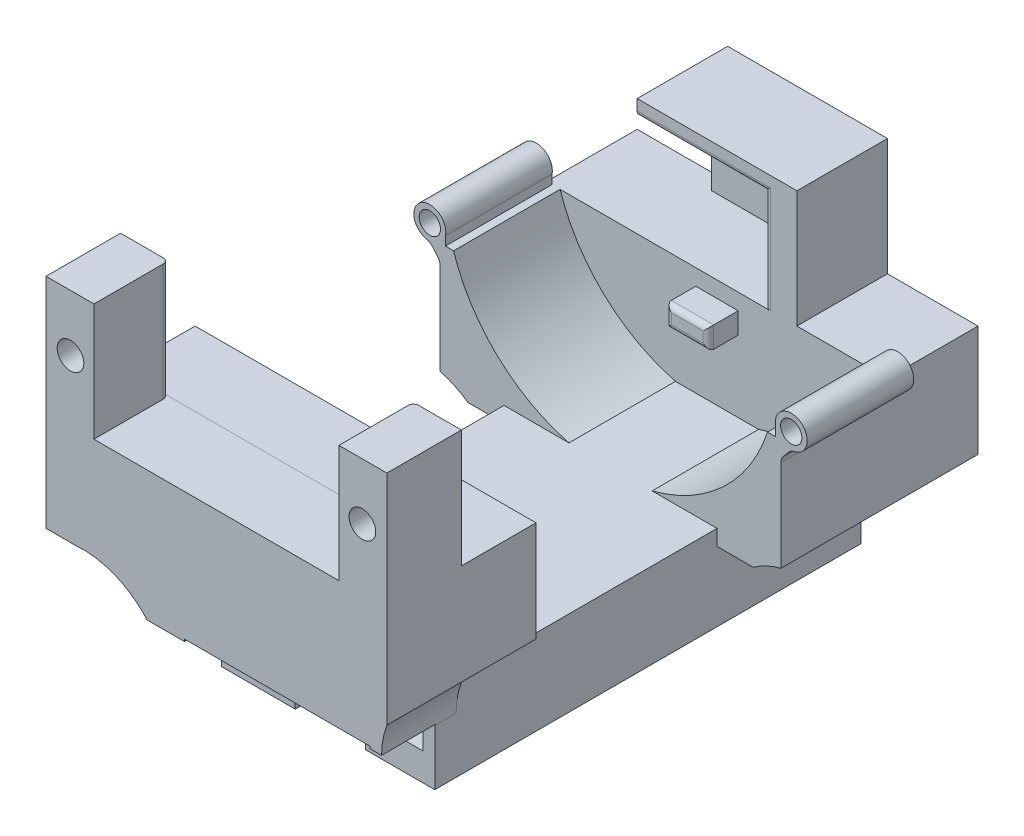
SolidWorks part; units mm, degrees
ref_plane "Front Plane" through (0, 0, 0) normal (0, 0, 1) x (1, 0, 0)
ref_plane "Top Plane" through (0, 0, 0) normal (0, 1, 0) x (1, 0, 0)
ref_plane "Right Plane" through (0, 0, 0) normal (1, 0, 0) x (0, 0, -1)
sketch "Sketch1" plane through (0, 0, 0) normal (0, 0, 1) x (1, 0, 0)
  line L0 (-6.3496, 0) -> (-0.9496, 0)
  line L1 (-0.9496, 0) -> (-0.9496, -2.6)
  line L2 (-0.9496, -2.6) -> (-7.8496, -2.6)
  line L3 (-7.8496, -2.6) -> (-7.8496, 5.4)
  line L4 (-7.8496, 5.4) -> (12.1504, 5.4)
  line L5 (12.1504, 5.4) -> (12.1504, -2.6)
  line L6 (12.1504, -2.6) -> (5.6504, -2.6)
  line L7 (5.6504, -2.6) -> (5.6504, 0)
  line L8 (5.6504, 0) -> (11.0504, 0)
  line L9 (11.0504, 0) -> (11.0504, 2.9)
  line L10 (11.0504, 2.9) -> (-6.3496, 2.9)
  line L11 (-6.3496, 2.9) -> (-6.3496, 0)
  dimension "D1" = 2.6
  dimension "D2" = 5.4
  dimension "D3" = 5.4
  dimension "D4" = 6.6
  dimension "D6" = 8
  dimension "D7" = 20
  dimension "D8" = 2.9
extrude "Boss-Extrude1" add sketch "Sketch1" along normal blind 50
sketch "Sketch2" plane through (0, 0, 50) normal (0, 0, 1) x (1, 0, 0)
  line L0 (12.1504, 5.4) -> (-7.8496, 5.4) construction
  line L2 (-19.3496, 25.9) -> (-19.3496, 5.4)
  line L3 (-19.3496, 5.4) -> (12.6504, 5.4)
  line L4 (12.6504, 25.9) -> (12.6504, 5.4)
  line L5 (-7.8496, 5.4) -> (-7.8496, -2.6) construction
  line L6 (-14.8496, 25.9) -> (-14.8496, 14.9)
  line L7 (-14.8496, 14.9) -> (8.1504, 14.9)
  line L8 (8.1504, 14.9) -> (8.1504, 25.9)
  line L9 (-19.3496, 25.9) -> (-14.8496, 25.9)
  line L10 (8.1504, 25.9) -> (12.6504, 25.9)
  circle A0 centre (10.3504, 20.6) radius 1.25
  circle A1 centre (-17.0496, 20.6) radius 1.25
  dimension "D8" = 5.3
  dimension "D1" = 0
  dimension "D2" = 32
  dimension "D3" = 11.5
  dimension "D4" = 11
  dimension "D5" = 11
  dimension "D6" = 4.5
  dimension "D7" = 4.5
  dimension "D9" = 5.3
  dimension "D10" = 2.3
  dimension "D11" = 2.3
  dimension "D12" = 20.5
extrude "Boss-Extrude2" add sketch "Sketch2" against normal blind 7
fillet "Fillet1" radius 8 2 edges at (-7.8496, 5.4, 46.5) (12.1504, 5.4, 46.5)
sketch "Sketch4" plane through (0, 0, 0) normal (0, 0, -1) x (-1, 0, 0)
  line L2 (-18.1504, 15.6) -> (-18.1504, 5.1)
  line L3 (-18.1504, 5.1) -> (13.8496, 5.1)
  line L4 (13.8496, 15.6) -> (13.8496, 5.1)
  line L5 (-18.1504, 15.6) -> (-9.6504, 15.6)
  line L6 (-9.6504, 26.6) -> (5.3496, 26.6)
  line L7 (-9.6504, 26.6) -> (-9.6504, 15.6)
  line L9 (5.3496, 26.6) -> (5.3496, 15.6)
  line L10 (5.3496, 15.6) -> (13.8496, 15.6)
  dimension "D1" = 11
  dimension "D2" = 11
  dimension "D3" = 15
  dimension "D4" = 8.5
  dimension "D5" = 21.5
  dimension "D6" = 8.5
extrude "Boss-Extrude3" add sketch "Sketch4" against normal blind 8.5
sketch "Sketch7" plane through (0, 0, 8.5) normal (0, 0, 1) x (1, 0, 0)
  line L0 (-5.3496, 15.6) -> (-5.3496, 26.6) construction
  line L1 (-5.3496, 25.1) -> (6.6504, 25.1)
  line L2 (-5.3496, 25.1) -> (-5.3496, 15.6)
  line L3 (-5.3496, 15.6) -> (6.6504, 15.6)
  line L4 (6.6504, 25.1) -> (6.6504, 15.6)
  line L5 (-5.3496, 26.6) -> (9.6504, 26.6) construction
  line L8 (18.1504, 15.6) -> (18.1504, 5.1) construction
  dimension "D1" = 1.5
  dimension "D2" = 11.5
extrude "Cut-Extrude1" cut sketch "Sketch7" against normal blind 7
sketch "Sketch8" plane through (0, 0, 8.5) normal (0, 0, 1) x (1, 0, 0)
  line L0 (12.1504, 5.4) -> (-7.8496, 5.4) construction
  line L1 (-13.8496, 15.6) -> (-12.5877, 15.6)
  line L2 (18.1504, 15.6) -> (18.1504, 5.1) construction
  line L3 (18.1504, 15.6) -> (18.1504, 3.938)
  line L4 (18.1504, 3.938) -> (-13.8496, 3.938)
  line L5 (-13.8496, 3.938) -> (-13.8496, 15.6)
  line L6 (16.8884, 15.6) -> (18.1504, 15.6)
  arc A0 (-12.5877, 15.6) -> (16.8884, 15.6) centre (2.1504, 20.4) ccw
  dimension "D1" = 15
  dimension "D2" = 16
extrude "Boss-Extrude4" add sketch "Sketch8" along normal blind 10
sketch "Sketch9" plane through (0, 0, 8.5) normal (0, 0, 1) x (1, 0, 0)
  line L0 (-13.8496, 15.6) -> (-13.8496, 3.938) construction
  line L1 (0.1604, 14.09) -> (4.1404, 14.09)
  line L2 (0.1604, 14.09) -> (0.1604, 12.11)
  line L3 (0.1604, 12.11) -> (4.1404, 12.11)
  line L4 (4.1404, 14.09) -> (4.1404, 12.11)
  line L5 (-5.3496, 26.6) -> (9.6504, 26.6) construction
  dimension "D1" = 3.98
  dimension "D2" = 1.98
  dimension "D3" = 14.01
  dimension "D4" = 12.51
extrude "Boss-Extrude5" add sketch "Sketch9" along normal blind 2.8
sketch "Sketch11" plane through (0, 0, 43) normal (0, 0, -1) x (-1, 0, 0)
  line L0 (19.3496, 5.4) -> (15.8496, 5.4) construction
  line L1 (-12.6504, 14.8531) -> (19.3496, 14.8531)
  line L2 (-12.6504, 14.8531) -> (-12.6504, 5.4)
  line L3 (-12.6504, 5.4) -> (19.3496, 5.4)
  line L4 (19.3496, 14.8531) -> (19.3496, 5.4)
  line L5 (19.3496, 25.9) -> (19.3496, 5.4) construction
extrude "Boss-Extrude6" add sketch "Sketch11" along normal blind 7
sketch "Sketch16" plane through (0, 0, 18.5) normal (0, 0, 1) x (1, 0, 0)
  line L0 (-13.3468, 15.6019) -> (-13.8468, 15.6019)
  line L1 (-13.3468, 15.6019) -> (-13.3468, 16.4404)
  line L2 (17.652, 15.6) -> (18.1504, 15.6)
  line L3 (18.1504, 15.6) -> (16.8884, 15.6) construction
  line L4 (17.652, 16.4221) -> (17.652, 15.6)
  line L5 (18.1504, 15.6) -> (18.1504, 14.1)
  line L6 (18.1504, 3.938) -> (18.1504, 15.6) construction
  line L7 (18.1504, 14.1) -> (19.1163, 15.2476)
  line L8 (-13.8468, 15.6019) -> (-13.8496, 14.1)
  line L9 (-13.8496, 15.6) -> (-13.8496, 3.938) construction
  line L10 (-13.8496, 14.1) -> (-14.815, 15.2476)
  circle A0 centre (-14.815, 16.7476) radius 1
  arc A1 (-13.3468, 16.4404) -> (-14.815, 15.2476) centre (-14.815, 16.7476) ccw
  circle A2 centre (19.1163, 16.7476) radius 1
  arc A3 (19.1163, 15.2476) -> (17.652, 16.4221) centre (19.1163, 16.7476) ccw
  dimension "D1" = 1.5
  dimension "D2" = 1.5
extrude "Boss-Extrude7" add sketch "Sketch16" against normal blind 10
fillet "Fillet2" radius 1 4 edges at (19.1163, 15.2476, 13.5) (18.1504, 14.1, 13.5) (-14.815, 15.2476, 13.5) (-13.8496, 14.1, 13.5)
fillet "Fillet4" radius 0.5 4 edges at (2.1504, 12.11, 11.3) (4.1404, 13.1, 11.3) (0.1604, 13.1, 11.3) (2.1504, 14.09, 11.3)
fillet "Fillet5" radius 0.5 2 edges at (6.6504, 20.35, 8.5) (0.6504, 25.1, 8.5)
fillet "Fillet6" radius 0.5 2 edges at (-14.8496, 20.4, 43) (8.1504, 20.4, 43)
sketch "Sketch17" plane through (0, 0, 50) normal (0, 0, 1) x (1, 0, 0)
  circle A0 centre (-15.8951, -2.5695) radius 8
  circle A1 centre (20.211, -2.5695) radius 8
extrude "Cut-Extrude2" cut sketch "Sketch17" against normal through all
sketch "Sketch18" plane through (0, 0, 50) normal (0, 0, 1) x (1, 0, 0)
  line L1 (-11.5489, 2.6964) -> (15.3565, 2.6964)
  line L2 (-11.5489, 2.6964) -> (-11.5489, -3.2277)
  line L3 (-11.5489, -3.2277) -> (15.3565, -3.2277)
  line L4 (15.3565, 2.6964) -> (15.3565, -3.2277)
extrude "Cut-Extrude3" cut sketch "Sketch18" against normal blind 5
sketch "Sketch19" plane through (0, 0, 0) normal (0, 0, -1) x (-1, 0, 0)
  line L1 (-15.7679, 2.573) -> (11.878, 2.573)
  line L2 (-15.7679, 2.573) -> (-15.7679, -5.2024)
  line L3 (-15.7679, -5.2024) -> (11.878, -5.2024)
  line L4 (11.878, 2.573) -> (11.878, -5.2024)
extrude "Cut-Extrude4" cut sketch "Sketch19" against normal blind 5
